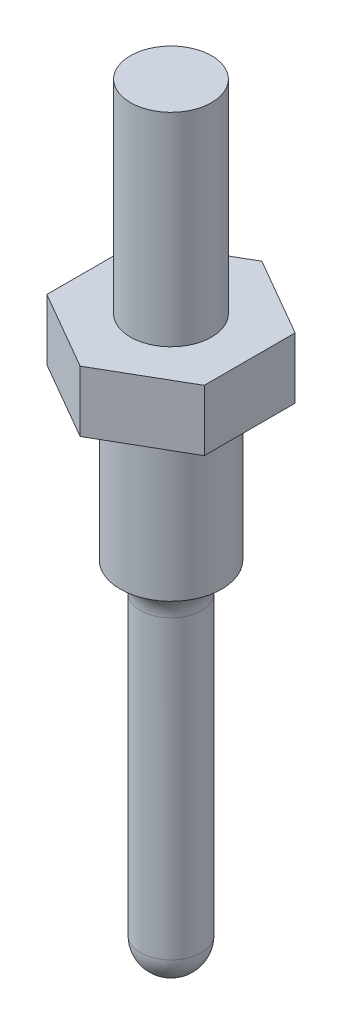
SolidWorks part; units mm, degrees
ref_plane "Front Plane" through (0, 0, 0) normal (0, 0, 1) x (1, 0, 0)
ref_plane "Top Plane" through (0, 0, 0) normal (0, 1, 0) x (1, 0, 0)
ref_plane "Right Plane" through (0, 0, 0) normal (1, 0, 0) x (0, 0, -1)
sketch "Sketch1" plane through (0, 0, 0) normal (0, 1, 0) x (1, 0, 0)
  circle A0 centre (0, 0) radius 3
  dimension "D1" = 6
extrude "Boss-Extrude1" add sketch "Sketch1" along normal blind 35
fillet "Fillet1" radius 3 1 edges at (0, 0, 3)
sketch "Sketch2" plane through (0, 35, 0) normal (0, 1, 0) x (1, 0, 0)
  circle A0 centre (0, 0) radius 5
  dimension "D1" = 10
extrude "Boss-Extrude2" add sketch "Sketch2" along normal blind 15
sketch "Sketch3" plane through (0, 50, 0) normal (0, 1, 0) x (1, 0, 0)
  line L0 (0, 0) -> (0, -8.9489) construction
  line L1 (7.75, -4.4745) -> (7.75, 4.4745)
  line L2 (7.75, 4.4745) -> (0, 8.9489)
  line L3 (0, 8.9489) -> (-7.75, 4.4745)
  line L4 (-7.75, 4.4745) -> (-7.75, -4.4745)
  line L5 (-7.75, -4.4745) -> (0, -8.9489)
  line L6 (0, -8.9489) -> (7.75, -4.4745)
  circle A0 centre (0, 0) radius 7.75 construction
  dimension "D1" = 15.5
extrude "Boss-Extrude3" add sketch "Sketch3" along normal blind 6
sketch "Sketch4" plane through (0, 56, 0) normal (0, 1, 0) x (1, 0, 0)
  circle A0 centre (0, 0) radius 4
  dimension "D1" = 8
extrude "Boss-Extrude4" add sketch "Sketch4" along normal blind 20
fillet "Fillet2" radius 3 1 edges at (0, 35, 3)
